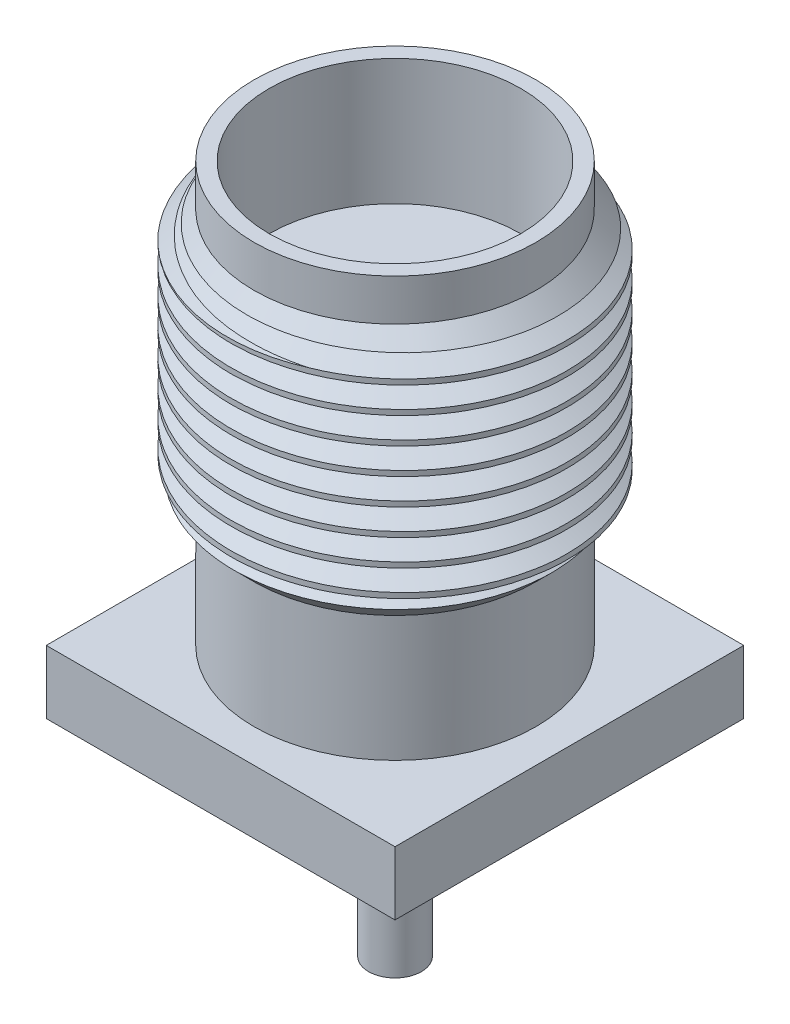
SolidWorks part; units mm, degrees
ref_plane "Front Plane" through (0, 0, 0) normal (0, 0, 1) x (1, 0, 0)
ref_plane "Top Plane" through (0, 0, 0) normal (0, 1, 0) x (1, 0, 0)
ref_plane "Right Plane" through (0, 0, 0) normal (1, 0, 0) x (0, 0, -1)
ref_plane "Plane1" through (0, 0, 0) normal (0, 0, -1) x (-1, 0, 0)
sketch "Sketch1" plane through (0, 0, 0) normal (0, 0, -1) x (-1, 0, 0)
  line L0 (-2.667, 4.1529) -> (0, 4.1529)
  line L1 (0, 4.1529) -> (0, 7.3342)
  line L2 (0, 7.3342) -> (-0.4445, 7.3342)
  line L3 (-0.635, 7.3342) -> (-2.3812, 7.3342)
  line L4 (-2.3812, 7.3342) -> (-2.3812, 9.7155)
  line L5 (-2.3812, 9.7155) -> (-2.667, 9.7155)
  line L6 (-2.667, 9.7155) -> (-2.667, 8.9281)
  line L7 (-2.667, 8.9281) -> (-3.175, 8.4201)
  line L8 (-3.175, 8.4201) -> (-3.175, 4.6609)
  line L9 (-3.175, 4.6609) -> (-2.667, 4.1529)
  line L10 (0, 4.1529) -> (0, 9.7155) construction
  arc A0 (-0.4445, 7.3342) -> (-0.5398, 7.3839) centre (-0.5581, 7.2327) ccw
  arc A1 (-0.5398, 7.3839) -> (-0.635, 7.3342) centre (-0.5214, 7.2326) ccw
revolve "Revolve1" add sketch "Sketch1" angle 360 about L10 reverse direction yes
sketch "Sketch2" plane through (0, 7.3342, 0) normal (0, 1, 0) x (-1, 0, 0)
  circle A0 centre (0, 0) radius 0.4445
extrude "Cut-Extrude1" cut sketch "Sketch2" against normal blind 2.3876
sketch "Sketch3" plane through (0, 4.1529, 0) normal (0, -1, 0) x (1, 0, 0)
  circle A0 centre (0, 0) radius 2.667
extrude "Boss-Extrude1" add sketch "Sketch3" along normal blind 2.3749
sketch "Sketch4" plane through (0, 1.778, 0) normal (0, -1, 0) x (1, 0, 0)
  line L0 (-3.3, -3.3) -> (-3.3, 3.3)
  line L1 (-3.3, 3.3) -> (3.3, 3.3)
  line L2 (3.3, 3.3) -> (3.3, -3.3)
  line L3 (3.3, -3.3) -> (-3.3, -3.3)
  line L4 (0, 0) -> (0, -4.4059) construction
  line L5 (3.8841, 0) -> (-3.418, 0) construction
  point P7 (0, -3.3)
  point P10 (3.3, 0)
  dimension "D1" = 6.6
extrude "Boss-Extrude2" add sketch "Sketch4" along normal blind 1.2
hole_wizard "#8 Clearance Hole1" positions "Sketch11" profile "Sketch10" hole size "#8" standard "ANSI Inch"
sketch "Sketch11" plane through (0, 0.578, 0) normal (0, -1, 0) x (-1, 0, 0)
  point P0 (0, 0)
sketch "Sketch10" plane through (0, 0.578, 0) normal (1, 0, 0) x (0, 0, -1)
  line L0 (0, 0) -> (0, 0.1016)
  line L1 (0, 0.1016) -> (2.159, 0.1016)
  line L2 (2.159, 0.1016) -> (2.159, 0)
  line L5 (2.159, 0) -> (0, 0)
  line L10 (0, 0.1016) -> (-2.159, 0.1016) construction
  line L11 (0, -6.35) -> (0, 107.95) construction
  dimension "Hole Dia." = 4.318
  dimension "Hole Depth" = 0.1016
  dimension "Drill Angle" = 180
sketch "Sketch12" plane through (0, 0, 0) normal (0, 0, 1) x (1, 0, 0)
  line L0 (0.5, 0.6796) -> (0, 0.6796)
  line L1 (0, 0.6796) -> (0, -3.3204)
  line L2 (0, -3.3204) -> (0.5, -3.3204)
  line L3 (0.5, -3.3204) -> (0.5, 0.6796)
  line L4 (0, 0.6796) -> (0, -3.3204) construction
  line L6 (-2.159, 0.6796) -> (2.159, 0.6796) construction
  dimension "D1" = 0.5
  dimension "D2" = 4
revolve "Revolve2" add sketch "Sketch12" angle 360 about L4 reverse direction yes
ref_plane "Plane2" through (0, 4.1529, 0) normal (0, 1, 0) x (1, 0, 0)
sketch "Sketch13" plane through (0, 4.1529, 0) normal (0, 1, 0) x (1, 0, 0)
  circle A0 centre (0, 0) radius 3.175 construction
  circle A1 centre (0, 0) radius 3.175
sketch "Sketch14" plane through (0, 0, 0) normal (1, 0, 0) x (0, 0, -1)
  line L0 (-3.175, 3.9529) -> (-2.8286, 4.1529)
  line L2 (-2.8286, 4.1529) -> (-3.175, 4.3529)
  line L3 (-3.175, 4.3529) -> (-3.175, 3.9529)
  line L4 (-3.175, 8.4201) -> (-3.175, 4.6609) construction
  line L6 (2.9337, 4.1529) -> (-2.9337, 4.1529) construction
  point P8 (-3.175, 4.1529)
  dimension "D1" = 0.4
  dimension "D2" = 60
  dimension "D3" = 60
curve "Helix/Spiral1" pitch 0.5 height 5 radius 3.175 left hand yes centre (0, 4.1529, 0) axis (0, 1, 0) start towards (0, 0, 1)
sweep "Cut-Sweep4" cut profiles "Sketch14" path "Helix/Spiral1" align with end faces yes
